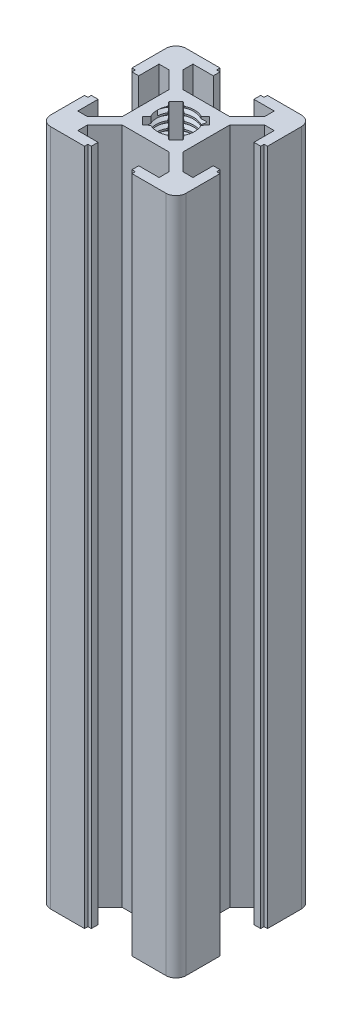
SolidWorks part; units mm, degrees
material "3.3547 (EN-AW 5083)"
ref_plane "Płaszczyzna przednia" through (0, 0, 0) normal (0, 0, 1) x (1, 0, 0)
ref_plane "Płaszczyzna górna" through (0, 0, 0) normal (0, 1, 0) x (1, 0, 0)
ref_plane "Płaszczyzna prawa" through (0, 0, 0) normal (1, 0, 0) x (0, 0, -1)
sketch "Szkic1" plane through (0, 0, 0) normal (0, 1, 0) x (1, 0, 0)
  line L0 (0, 10) -> (0, -10) construction
  line L1 (4.5, -4.5) -> (-4.5, -4.5)
  line L2 (4.5, -4.5) -> (4.5, 4.5)
  line L3 (4.5, 4.5) -> (-4.5, 4.5)
  line L4 (-4.5, -4.5) -> (-4.5, 4.5)
  line L5 (4.5, -4.5) -> (-4.5, 4.5) construction
  line L6 (4.5, 4.5) -> (-4.5, -4.5) construction
  line L7 (8.5, -10) -> (-8.5, -10)
  line L8 (10, -8.5) -> (10, 8.5)
  line L9 (8.5, 10) -> (-8.5, 10)
  line L10 (-10, -8.5) -> (-10, 8.5)
  line L11 (10, -10) -> (-10, 10) construction
  line L12 (10, 10) -> (-10, -10) construction
  line L13 (3.5, 10) -> (-3.5, 10)
  line L14 (-3.5, 10) -> (-3.5, 9.5)
  line L15 (-3.5, 9.5) -> (-3, 9.5)
  line L16 (-3, 9.5) -> (-3, 8.5)
  line L17 (-3, 8.5) -> (-6, 8.5)
  line L18 (-6, 8.5) -> (-6, 7.06)
  line L19 (-6, 7.06) -> (-3.4405, 4.5)
  line L20 (-1.9445, 3.0052) -> (-3.0052, 1.9445)
  line L21 (-1.9445, 3.0052) -> (-1.2713, 2.4385)
  line L22 (-3.0052, 1.9445) -> (-2.4385, 1.2713)
  line L23 (3.5, 10) -> (3.5, 9.5)
  line L24 (3.5, 9.5) -> (3, 9.5)
  line L25 (3, 9.5) -> (3, 8.5)
  line L26 (3, 8.5) -> (6, 8.5)
  line L27 (6, 8.5) -> (6, 7.06)
  line L28 (6, 7.06) -> (3.4405, 4.5)
  line L29 (1.9445, 3.0052) -> (3.0052, 1.9445)
  line L30 (1.9445, 3.0052) -> (1.2713, 2.4385)
  line L31 (3.0052, 1.9445) -> (2.4385, 1.2713)
  line L32 (1.9445, 3.0052) -> (1.2713, 2.4385)
  line L33 (3.0052, 1.9445) -> (1.9445, 3.0052)
  line L34 (3.0052, 1.9445) -> (2.4385, 1.2713)
  line L35 (7.06, 6) -> (4.5, 3.4405)
  line L36 (8.5, 6) -> (7.06, 6)
  line L37 (8.5, 3) -> (8.5, 6)
  line L38 (9.5, 3) -> (8.5, 3)
  line L39 (9.5, 3.5) -> (9.5, 3)
  line L40 (10, 3.5) -> (9.5, 3.5)
  line L41 (10, -3.5) -> (9.5, -3.5)
  line L42 (9.5, -3.5) -> (9.5, -3)
  line L43 (9.5, -3) -> (8.5, -3)
  line L44 (8.5, -3) -> (8.5, -6)
  line L45 (8.5, -6) -> (7.06, -6)
  line L46 (7.06, -6) -> (4.5, -3.4405)
  line L47 (3.0052, -1.9445) -> (2.4385, -1.2713)
  line L48 (3.0052, -1.9445) -> (1.9445, -3.0052)
  line L49 (1.9445, -3.0052) -> (1.2713, -2.4385)
  line L50 (3.0052, -1.9445) -> (2.4385, -1.2713)
  line L51 (1.9445, -3.0052) -> (3.0052, -1.9445)
  line L52 (1.9445, -3.0052) -> (1.2713, -2.4385)
  line L53 (6, -7.06) -> (3.4405, -4.5)
  line L54 (6, -8.5) -> (6, -7.06)
  line L55 (3, -8.5) -> (6, -8.5)
  line L56 (3, -9.5) -> (3, -8.5)
  line L57 (3.5, -9.5) -> (3, -9.5)
  line L58 (3.5, -10) -> (3.5, -9.5)
  line L59 (-3.5, -10) -> (-3.5, -9.5)
  line L60 (-3.5, -9.5) -> (-3, -9.5)
  line L61 (-3, -9.5) -> (-3, -8.5)
  line L62 (-3, -8.5) -> (-6, -8.5)
  line L63 (-6, -8.5) -> (-6, -7.06)
  line L64 (-6, -7.06) -> (-3.4405, -4.5)
  line L65 (-1.9445, -3.0052) -> (-1.2713, -2.4385)
  line L66 (-1.9445, -3.0052) -> (-3.0052, -1.9445)
  line L67 (-3.0052, -1.9445) -> (-2.4385, -1.2713)
  line L68 (-1.9445, -3.0052) -> (-1.2713, -2.4385)
  line L69 (-3.0052, -1.9445) -> (-1.9445, -3.0052)
  line L70 (-3.0052, -1.9445) -> (-2.4385, -1.2713)
  line L71 (-7.06, -6) -> (-4.5, -3.4405)
  line L72 (-8.5, -6) -> (-7.06, -6)
  line L73 (-8.5, -3) -> (-8.5, -6)
  line L74 (-9.5, -3) -> (-8.5, -3)
  line L75 (-9.5, -3.5) -> (-9.5, -3)
  line L76 (-10, -3.5) -> (-9.5, -3.5)
  line L77 (-10, 3.5) -> (-9.5, 3.5)
  line L78 (-9.5, 3.5) -> (-9.5, 3)
  line L79 (-9.5, 3) -> (-8.5, 3)
  line L80 (-8.5, 3) -> (-8.5, 6)
  line L81 (-8.5, 6) -> (-7.06, 6)
  line L82 (-7.06, 6) -> (-4.5, 3.4405)
  line L83 (-3.0052, 1.9445) -> (-2.4385, 1.2713)
  line L84 (-3.0052, 1.9445) -> (-1.9445, 3.0052)
  line L85 (-1.9445, 3.0052) -> (-1.2713, 2.4385)
  circle A0 centre (0, 0) radius 2.75
  arc A1 (10, -8.5) -> (8.5, -10) centre (8.5, -8.5) cw
  arc A2 (-10, -8.5) -> (-8.5, -10) centre (-8.5, -8.5) ccw
  arc A3 (10, 8.5) -> (8.5, 10) centre (8.5, 8.5) ccw
  arc A4 (-8.5, 10) -> (-10, 8.5) centre (-8.5, 8.5) ccw
  point P16 (0, 10)
  point P37 (-2.4749, 2.4749)
  dimension "D1" = 5.5
  dimension "D12" = 1.5
  dimension "D2" = 9
  dimension "D3" = 20
  dimension "D4" = 20
  dimension "D5" = 7
  dimension "D6" = 0.5
  dimension "D7" = 0.5
  dimension "D8" = 1
  dimension "D9" = 3
  dimension "D10" = 1.44
  dimension "D11" = 3.62
  dimension "D13" = 1.5
  dimension "D14" = 3.5
  dimension "D15" = 0.88
  dimension "D16" = 4
extrude "Dodanie-wyciągnięcie1" add sketch "Szkic1" along normal blind 100 contours L9 A4 L10 L77 L78 L79 L80 L81 L82 L4 L3 L19 L18 L17 L16 L15 L14 | L8 A3 L9 L23 L24 L25 L26 L27 L28 L3 L2 L35 L36 L37 L38 L39 L40 | L4 L1 L2 L3 A0 L47 L48 L49 L65 L66 L67 L22 L20 L21 L30 L29 L31 | L10 A2 L7 L59 L60 L61 L62 L63 L64 L1 L4 L71 L72 L73 L74 L75 L76 | A1 L8 L41 L42 L43 L44 L45 L46 L2 L1 L53 L54 L55 L56 L57 L58 L7 region at (7.2228, 0, 7.2228) region at (3.9703, 0, 4.3727) region at (-7.2228, 0, 7.2228) region at (7.2228, 0, -7.2228) region at (-7.2228, 0, -7.2228)
thread "Thread1" pitch 1 method cut profile "Thread Profile1" start angle 0, offset 0, length 30, pitch 1, diameter 5.5
ref_plane "Plane1" through (-2.75, 100, 0) normal (0, 0, 1) x (-1, 0, 0)
sketch "Thread Profile1" plane through (-2.75, 100, 0) normal (0, 0, 1) x (-1, 0, 0)
  line L0 (0, 0) -> (0, 1) construction
  line L1 (0, 0) -> (0.5413, 0.3125)
  line L2 (0.5413, 0.3125) -> (0.5413, 0.4375)
  line L3 (0.5413, 0.4375) -> (0, 0.75)
  line L4 (0.5413, 0.375) -> (0, 0.375) construction
  line L11 (0, 0) -> (0, 0.75)
  point P2 (0, 0)
  dimension "Pitch" = 1
  dimension "Profile_Angle" = 60
  dimension "Profile_Land" = 0.125
  dimension "Profile_Height" = 0.5413
thread "Thread2" pitch 1 method cut profile "Thread Profile2" start angle 0, offset 0, length 30, pitch 1, diameter 5.5
ref_plane "Plane2" through (2.75, 0, 0) normal (0, 0, 1) x (1, 0, 0)
sketch "Thread Profile2" plane through (2.75, 0, 0) normal (0, 0, 1) x (1, 0, 0)
  line L0 (0, 0) -> (0, 1) construction
  line L1 (0, 0) -> (0.5413, 0.3125)
  line L2 (0.5413, 0.3125) -> (0.5413, 0.4375)
  line L3 (0.5413, 0.4375) -> (0, 0.75)
  line L4 (0.5413, 0.375) -> (0, 0.375) construction
  line L11 (0, 0) -> (0, 0.75)
  point P2 (0, 0)
  dimension "Pitch" = 1
  dimension "Profile_Angle" = 60
  dimension "Profile_Land" = 0.125
  dimension "Profile_Height" = 0.5413
